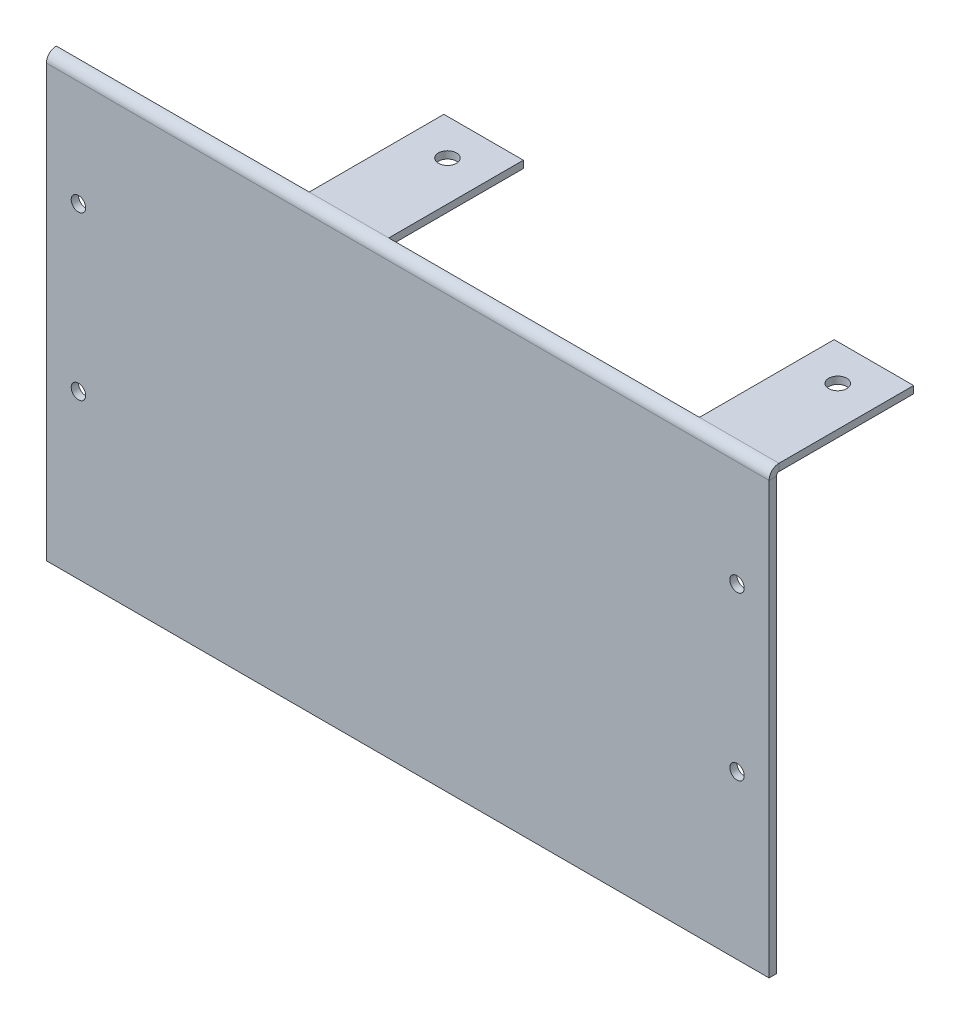
SolidWorks part; units mm, degrees
note: The reader was unsure of these and kept them because the rebuilt part matched: flange length of "Edge-Flange1".
material "5052-H34"
ref_plane "Front Plane" through (0, 0, 0) normal (0, 0, 1) x (1, 0, 0)
ref_plane "Top Plane" through (0, 0, 0) normal (0, 1, 0) x (1, 0, 0)
ref_plane "Right Plane" through (0, 0, 0) normal (1, 0, 0) x (0, 0, -1)
sketch "Sketch2" plane through (0, 0, 0) normal (0, 0, 1) x (1, 0, 0)
  line L1 (0, 0) -> (200, 0)
  line L2 (0, 0) -> (0, 120)
  line L3 (0, 120) -> (200, 120)
  line L4 (200, 0) -> (200, 120)
  dimension "D1" = 120
  dimension "D2" = 200
base flange "Base-Flange1" sketch "Sketch2" thickness 2 reverse thickness direction no parameters "D1"=0.7366
sketch "Sketch7" plane through (0, 0, 0) normal (0, 0, 1) x (1, 0, 0)
  line L0 (200, 120) -> (0, 120) construction
  line L1 (0, 120) -> (0, 0) construction
  line L2 (200, 0) -> (200, 120) construction
  circle A0 centre (8.87, 90) radius 2
  circle A1 centre (8.87, 45) radius 2
  circle A2 centre (191.13, 45) radius 2
  circle A3 centre (191.13, 90) radius 2
  dimension "D1" = 4
  dimension "D2" = 30
  dimension "D3" = 8.87
  dimension "D4" = 45
  dimension "D5" = 8.87
extrude "Cut-Extrude1" cut sketch "Sketch7" against normal up to next normal cut yes
edge flange "Edge-Flange1" sketch "Sketch10" flange angle 90 flange length 40 flange position material outside bend radius 0.7366 thickness 2 relief rectangular parameters "D6"=10
sketch "Sketch10" plane through (0, 120, -2) normal (0, -1, 0) x (-1, 0, 0)
  line L2 (-200, 0) -> (-200, 38)
  line L3 (-200, 38) -> (0, 38)
  line L4 (0, 38) -> (0, 0)
  line L6 (0, 0) -> (-200, 0) construction
  line L7 (0, 0) -> (-200, 0)
bend "EdgeBend1" bend radius 0.7366 bend angle 90 parameters "D5"=1
sketch "Sketch11" plane through (0, 122, 0) normal (0, 1, 0) x (1, 0, 0)
  line L0 (200, 30) -> (189, 30) construction
  line L1 (189, 40) -> (189, 2.7366) construction
  line L2 (81, 30) -> (0, 30) construction
  line L4 (200, 40) -> (200, 2.7366) construction
  line L5 (0, 2.7366) -> (0, 40) construction
  line L6 (0, 40) -> (200, 40) construction
  line L7 (0, 2.7366) -> (200, 2.7366) construction
  line L12 (178, 2.7366) -> (92, 2.7366)
  line L13 (178, 2.7366) -> (178, 40)
  line L14 (178, 40) -> (92, 40)
  line L15 (92, 2.7366) -> (92, 40)
  line L17 (70, 2.7366) -> (0, 2.7366)
  line L18 (70, 2.7366) -> (70, 40)
  line L19 (70, 40) -> (0, 40)
  line L20 (0, 2.7366) -> (0, 40)
  line L21 (81, 2.7366) -> (81, 40) construction
  circle A0 centre (189, 30) radius 2.5
  circle A1 centre (81, 30) radius 2.5
  point P12 (200, 21.3683)
  dimension "D1" = 5
  dimension "D2" = 108
  dimension "D3" = 10
  dimension "D4" = 22
  dimension "D5" = 22
  dimension "D6" = 11
extrude "Cut-Extrude2" cut sketch "Sketch11" against normal up to next normal cut yes
sketch "Bend-Lines1" [suppressed] plane through (0, 0, 0) normal (0, 1, 0) x (1, 0, 0)
sketch "Bounding-Box1" [suppressed] plane through (0, 0, 0) normal (0, 1, 0) x (1, 0, 0)
sheet metal parameters "Sheet-Metal1" thickness 2 parameters "D1"=0.7366
flat pattern "Flat-Pattern1" [suppressed]
sketch "Bend-Lines2" plane through (0, 0, 0) normal (0, 1, 0) x (1, 0, 0)
sketch "Bounding-Box2" [suppressed] plane through (0, 0, 0) normal (0, 1, 0) x (1, 0, 0)
sheet metal parameters "Sheet-Metal2" thickness 2 parameters "D1"=0.7366
flat pattern "Flat-Pattern1"
sketch "Bend-Lines2" plane through (0, 0, 0) normal (0, 1, 0) x (1, 0, 0)
sketch "Bounding-Box2" [suppressed] plane through (0, 0, 0) normal (0, 1, 0) x (1, 0, 0)
sheet metal parameters "Sheet-Metal3" thickness 2 parameters "D1"=0.7366
flat pattern "Flat-Pattern1" [suppressed]
sketch "Bend-Lines2" plane through (0, 0, 0) normal (0, 1, 0) x (1, 0, 0)
sketch "Bounding-Box2" [suppressed] plane through (0, 0, 0) normal (0, 1, 0) x (1, 0, 0)
bend of the flat pattern "Flatten-<EdgeBend1>1"
sheet metal parameters "Sheet-Metal4" thickness 2 parameters "D1"=0.7366
flat pattern "Flat-Pattern1"
sketch "Bend-Lines2" plane through (0, 0, 0) normal (0, 0, 1) x (1, 0, 0)
  line L0 (0, 120.6273) -> (200, 120.6273) construction
  line L1 (0, 120.6273) -> (200, 120.6273) construction
sketch3d "Bounding-Box2" [suppressed]
  line L0 (0, 0, 0) -> (200, 0, 0) construction
  line L1 (0, 159.2546, 0) -> (200, 159.2546, 0) construction
  line L2 (0, 0, 0) -> (0, 159.2546, 0) construction
  line L3 (200, 0, 0) -> (200, 159.2546, 0) construction
bend of the flat pattern "Flatten-<EdgeBend1>1"
